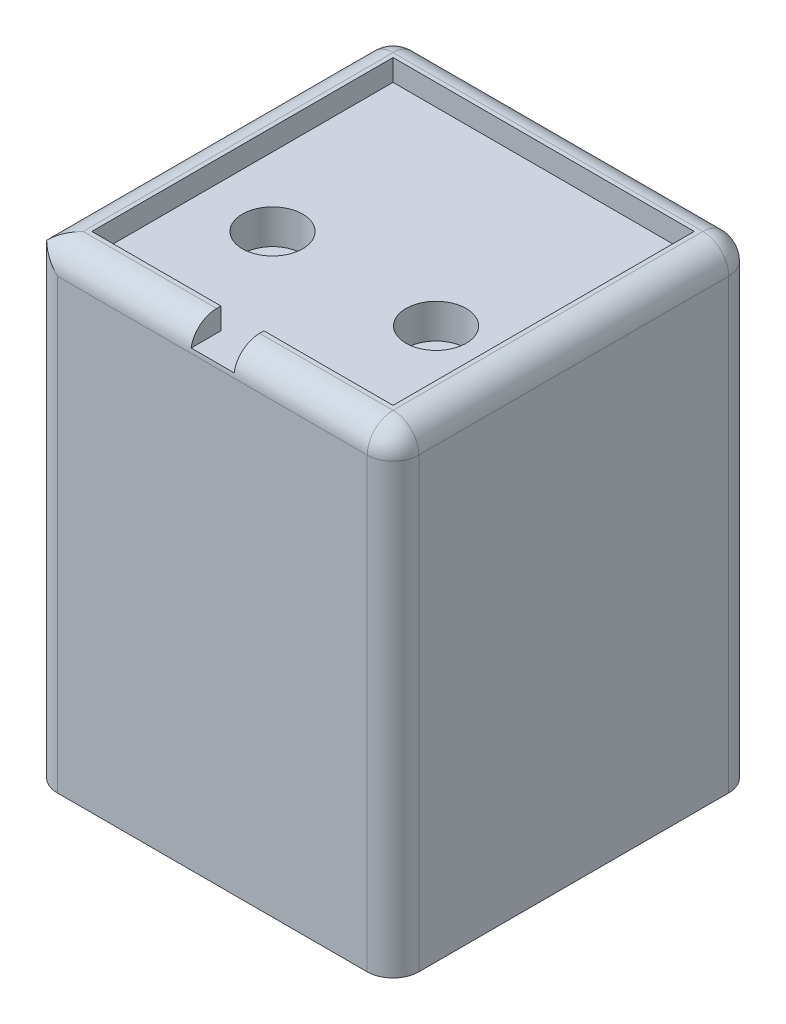
SolidWorks part; units mm, degrees
ref_plane "Front Plane" through (0, 0, 0) normal (0, 0, 1) x (1, 0, 0)
ref_plane "Top Plane" through (0, 0, 0) normal (0, 1, 0) x (1, 0, 0)
ref_plane "Right Plane" through (0, 0, 0) normal (1, 0, 0) x (0, 0, -1)
sketch "Sketch2" plane through (0, 0, 0) normal (0, 1, 0) x (1, 0, 0)
  line L1 (21, 21) -> (-21, 21)
  line L2 (21, 21) -> (21, -21)
  line L3 (21, -21) -> (-21, -21)
  line L4 (-21, 21) -> (-21, -21)
  line L5 (21, 21) -> (-21, -21) construction
  line L6 (21, -21) -> (-21, 21) construction
  point P0 (0, 0)
  dimension "D1" = 42
  dimension "D2" = 42
extrude "Boss-Extrude1" add sketch "Sketch2" along normal blind 55
sketch "Sketch3" plane through (0, 55, 0) normal (0, 1, 0) x (1, 0, 0)
  line L1 (17.5, 17.5) -> (-17.5, 17.5)
  line L2 (17.5, 17.5) -> (17.5, -17.5)
  line L3 (17.5, -17.5) -> (-17.5, -17.5)
  line L4 (-17.5, 17.5) -> (-17.5, -17.5)
  line L5 (17.5, 17.5) -> (-17.5, -17.5) construction
  line L6 (17.5, -17.5) -> (-17.5, 17.5) construction
  point P0 (0, 0)
  dimension "D1" = 35
  dimension "D2" = 35
extrude "Cut-Extrude1" cut sketch "Sketch3" against normal blind 2.5
sketch "Sketch4" plane through (0, 55, 0) normal (0, 1, 0) x (1, 0, 0)
  line L0 (-17.5, -17.5) -> (17.5, -17.5) construction
  line L1 (-2.5, -17.5) -> (2.5, -17.5)
  line L2 (-2.5, -17.5) -> (-2.5, -21)
  line L3 (-2.5, -21) -> (2.5, -21)
  line L4 (2.5, -17.5) -> (2.5, -21)
  line L5 (-21, -21) -> (21, -21) construction
  line L6 (21, -21) -> (21, 21) construction
  dimension "D1" = 5
  dimension "D2" = 18.5
extrude "Cut-Extrude2" cut sketch "Sketch4" against normal blind 2.5
fillet "Fillet1" radius 3 8 edges at (11.75, 55, 21) (21, 27.5, 21) (-21, 27.5, 21) (21, 27.5, -21) (-21, 27.5, -21) (-21, 55, 0) (0, 55, -21) (21, 55, 0)
sketch "Sketch5" plane through (0, 52.5, 0) normal (0, 1, 0) x (1, 0, 0)
  line L0 (-17.5, 17.5) -> (-17.5, -17.5) construction
  line L1 (17.5, 17.5) -> (-17.5, 17.5) construction
  line L2 (0, 17.5) -> (0, -20.958) construction
  line L3 (-2.5, -20.958) -> (2.5, -20.958) construction
  circle A0 centre (-9.5, -4.5) radius 3.5
  circle A1 centre (9.5, -4.5) radius 3.5
  dimension "D1" = 7
  dimension "D2" = 8
  dimension "D3" = 22
extrude "Cut-Extrude3" cut sketch "Sketch5" against normal blind 4
